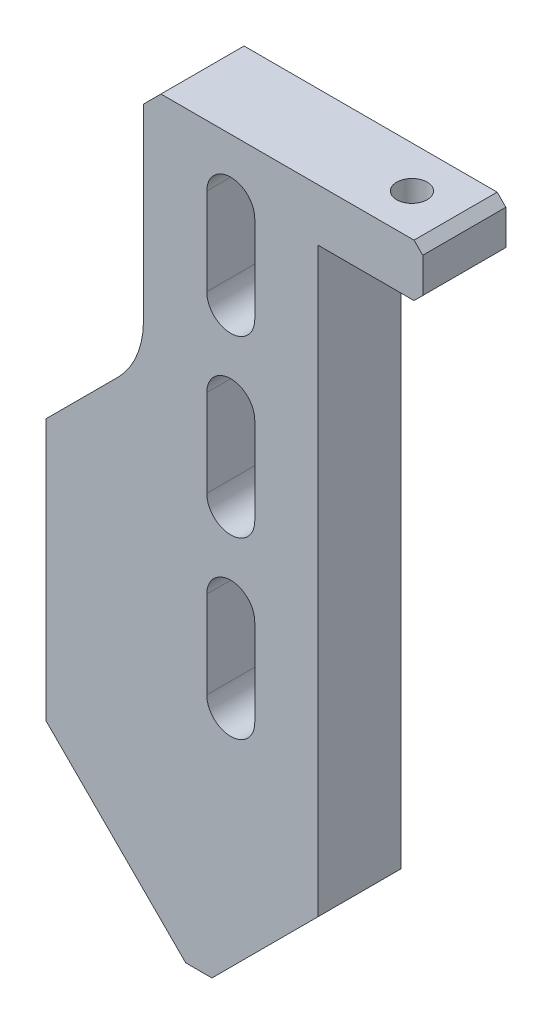
SolidWorks part; units mm, degrees
material "Plain Carbon Steel"
ref_plane "Front Plane" through (0, 0, 0) normal (0, 0, 1) x (1, 0, 0)
ref_plane "Top Plane" through (0, 0, 0) normal (0, 1, 0) x (1, 0, 0)
ref_plane "Right Plane" through (0, 0, 0) normal (1, 0, 0) x (0, 0, -1)
sketch "Sketch1" plane through (0, 0, 0) normal (0, 0, 1) x (1, 0, 0)
  line L0 (-191.4038, 11.3962) -> (-207.4038, 27.3962) construction
  line L1 (-207.4038, 27.3962) -> (-207.4038, 57.3962) construction
  line L2 (-196.2477, 68.5523) -> (-207.4038, 57.3962) construction
  line L3 (-196.2477, 96.1924) -> (-196.2477, 68.5523) construction
  line L4 (-164.2477, 96.1924) -> (-196.2477, 96.1924) construction
  line L5 (-164.2477, 90.1924) -> (-164.2477, 96.1924) construction
  line L6 (-176.2477, 90.1924) -> (-164.2477, 90.1924) construction
  line L7 (-176.2477, 90.1924) -> (-176.2477, 23.5523) construction
  line L8 (-176.2477, 23.5523) -> (-188.4038, 11.3962) construction
  line L9 (-191.4038, 11.3962) -> (-188.4038, 11.3962) construction
  line L10 (-191.4038, 11.3962) -> (-207.4038, 27.3962)
  line L11 (-207.4038, 27.3962) -> (-207.4038, 57.3962)
  line L12 (-196.2477, 68.5523) -> (-207.4038, 57.3962)
  line L13 (-196.2477, 96.1924) -> (-196.2477, 68.5523)
  line L14 (-164.2477, 96.1924) -> (-196.2477, 96.1924)
  line L15 (-164.2477, 90.1924) -> (-164.2477, 96.1924)
  line L16 (-176.2477, 90.1924) -> (-164.2477, 90.1924)
  line L17 (-176.2477, 90.1924) -> (-176.2477, 23.5523)
  line L18 (-176.2477, 23.5523) -> (-188.4038, 11.3962)
  line L19 (-191.4038, 11.3962) -> (-188.4038, 11.3962)
  line L20 (-168.7477, 96.1924) -> (-168.7477, 85.1924) construction
  line L21 (-170.2477, 96.1924) -> (-170.2477, 85.1924) construction
  line L22 (-171.7477, 96.1924) -> (-171.7477, 85.1924) construction
  line L23 (-168.7477, 96.1924) -> (-168.7477, 85.1924) construction
  line L24 (-170.2477, 96.1924) -> (-170.2477, 85.1924) construction
  line L25 (-171.7477, 96.1924) -> (-171.7477, 85.1924) construction
  line L26 (-183.4977, 39.1924) -> (-183.4977, 49.1924) construction
  line L27 (-188.9977, 39.1924) -> (-188.9977, 49.1924) construction
  line L28 (-183.4977, 59.1924) -> (-183.4977, 69.1924) construction
  line L29 (-188.9977, 59.1924) -> (-188.9977, 69.1924) construction
  line L30 (-183.4977, 79.1924) -> (-183.4977, 89.1924) construction
  line L31 (-188.9977, 79.1924) -> (-188.9977, 89.1924) construction
  line L32 (-183.4977, 39.1924) -> (-183.4977, 49.1924)
  line L33 (-188.9977, 39.1924) -> (-188.9977, 49.1924)
  line L34 (-183.4977, 59.1924) -> (-183.4977, 69.1924)
  line L35 (-188.9977, 59.1924) -> (-188.9977, 69.1924)
  line L36 (-183.4977, 79.1924) -> (-183.4977, 89.1924)
  line L37 (-188.9977, 79.1924) -> (-188.9977, 89.1924)
  arc A0 (-183.4977, 49.1924) -> (-188.9977, 49.1924) centre (-186.2477, 49.1924) ccw construction
  arc A1 (-188.9977, 39.1924) -> (-183.4977, 39.1924) centre (-186.2477, 39.1924) ccw construction
  arc A2 (-183.4977, 69.1924) -> (-188.9977, 69.1924) centre (-186.2477, 69.1924) ccw construction
  arc A3 (-188.9977, 59.1924) -> (-183.4977, 59.1924) centre (-186.2477, 59.1924) ccw construction
  arc A4 (-183.4977, 89.1924) -> (-188.9977, 89.1924) centre (-186.2477, 89.1924) ccw construction
  arc A5 (-188.9977, 79.1924) -> (-183.4977, 79.1924) centre (-186.2477, 79.1924) ccw construction
  arc A6 (-183.4977, 49.1924) -> (-188.9977, 49.1924) centre (-186.2477, 49.1924) ccw
  arc A7 (-188.9977, 39.1924) -> (-183.4977, 39.1924) centre (-186.2477, 39.1924) ccw
  arc A8 (-183.4977, 69.1924) -> (-188.9977, 69.1924) centre (-186.2477, 69.1924) ccw
  arc A9 (-188.9977, 59.1924) -> (-183.4977, 59.1924) centre (-186.2477, 59.1924) ccw
  arc A10 (-183.4977, 89.1924) -> (-188.9977, 89.1924) centre (-186.2477, 89.1924) ccw
  arc A11 (-188.9977, 79.1924) -> (-183.4977, 79.1924) centre (-186.2477, 79.1924) ccw
extrude "Boss-Extrude1" add sketch "Sketch1" along normal blind 4.7625 and the other way blind 4.7625
sketch "Sketch2" plane through (0, 96.1924, 0) normal (0, 1, 0) x (-1, 0, 0)
  circle A0 centre (170.2477, 0) radius 1.75
  dimension "D1" = 3.5
extrude "Cut-Extrude1" cut sketch "Sketch2" against normal through all
fillet "Fillet1" radius 10 1 edges at (-196.2477, 68.5523, 0)
chamfer "Chamfer1" distance 2 angle 45 1 edges at (-196.2477, 96.1924, 0)
chamfer "Chamfer2" distance 1 angle 45 2 edges at (-164.2477, 96.1924, 0) (-164.2477, 90.1924, 0)
